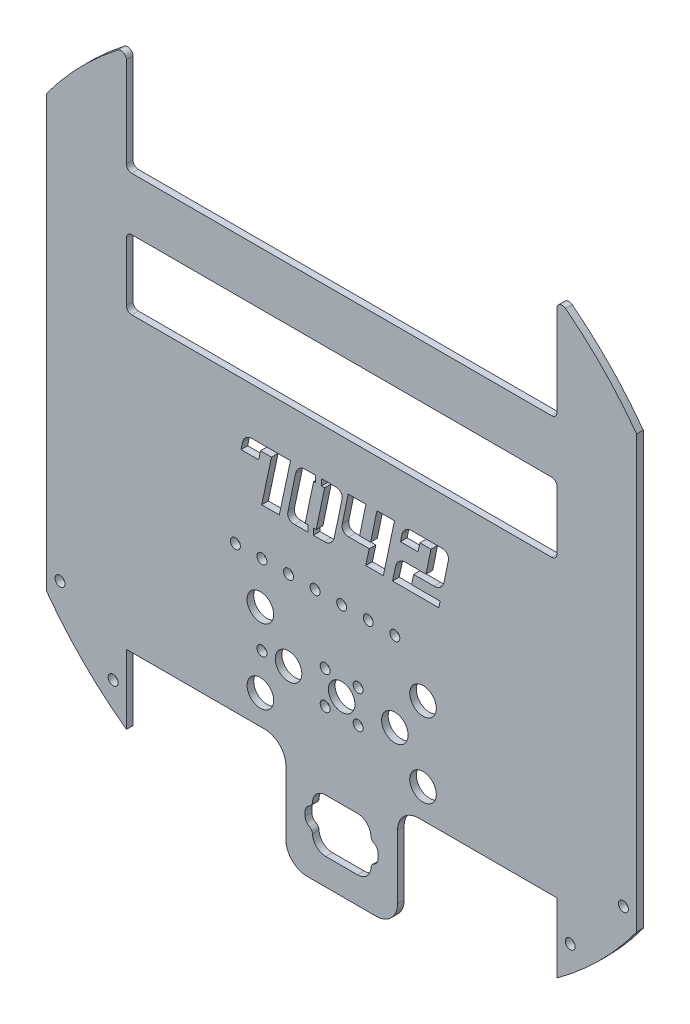
SolidWorks part; units mm, degrees
material "6061 Alloy"
ref_plane "Front Plane" through (0, 0, 0) normal (0, 0, 1) x (1, 0, 0)
ref_plane "Top Plane" through (0, 0, 0) normal (0, 1, 0) x (1, 0, 0)
ref_plane "Right Plane" through (0, 0, 0) normal (1, 0, 0) x (0, 0, -1)
sketch "Sketch1" plane through (0, 0, 0) normal (0, 0, 1) x (1, 0, 0)
  line L1 (-140.9655, 145.0225) -> (-102.8655, 145.0225)
  line L2 (-140.9655, 145.0225) -> (-140.9655, -145.0225)
  line L3 (-140.9655, -145.0225) -> (-102.8655, -145.0225)
  line L4 (-102.8655, 145.0225) -> (-102.8655, -145.0225)
  line L5 (-140.9655, 145.0225) -> (-102.8655, -145.0225) construction
  line L6 (-140.9655, -145.0225) -> (-102.8655, 145.0225) construction
  line L7 (-140.9655, 31.75) -> (140.9655, 31.75)
  line L8 (-140.9655, 31.75) -> (-140.9655, -31.75)
  line L9 (-140.9655, -31.75) -> (140.9655, -31.75)
  line L10 (140.9655, 31.75) -> (140.9655, -31.75)
  line L11 (-140.9655, 31.75) -> (140.9655, -31.75) construction
  line L12 (-140.9655, -31.75) -> (140.9655, 31.75) construction
  line L13 (102.8655, 145.0225) -> (140.9655, 145.0225)
  line L14 (102.8655, 145.0225) -> (102.8655, -145.0225)
  line L15 (102.8655, -145.0225) -> (140.9655, -145.0225)
  line L16 (140.9655, 145.0225) -> (140.9655, -145.0225)
  line L17 (102.8655, 145.0225) -> (140.9655, -145.0225) construction
  line L18 (102.8655, -145.0225) -> (140.9655, 145.0225) construction
  line L19 (-140.9655, -31.75) -> (140.9655, -31.75)
  line L20 (-140.9655, -31.75) -> (-140.9655, -69.85)
  line L21 (-140.9655, -69.85) -> (140.9655, -69.85)
  line L22 (140.9655, -31.75) -> (140.9655, -69.85)
  circle A0 centre (0, 0) radius 177.8
  circle A7 centre (0, -38.1) radius 25.4 construction
  circle A8 centre (-25.4, -38.1) radius 2.3813
  circle A9 centre (25.4, -38.1) radius 2.3813
  circle A10 centre (0, -38.1) radius 2.3812
  point P3 (-121.9155, 0)
  point P12 (121.9155, 0)
  dimension "D1" = 355.6
  dimension "D5" = 50.8
  dimension "D6" = 38.1
  dimension "D7" = 281.9311
  dimension "D10" = 4.7625
  dimension "D8" = 4.7625
  dimension "D9" = 4.7625
  dimension "D2" = 38.1
  dimension "D3" = 38.1
  dimension "D4" = 63.5
  dimension "D12" = 38.1
extrude "Boss-Extrude1" add sketch "Sketch1" along normal blind 3.175 contours L4 A0 L2 L7 | L2 L9 L4 L7 | L14 L7 L4 L9 A8 | L2 A0 L4 L9 | L16 A0 L14 L7 | L7 L14 L9 L10 | L14 A0 L16 L9 | L19 A10 L9 L4 L21 L14 A9 A8 | L2 L21 L4 L9 | L14 L21 L16 L9 region at (-120.723, 80.7079, 0) region at (0, 0, 0) region at (-121.9155, 0, 0) region at (120.723, 80.7079, 0) region at (-119.9486, -100.1295, 0) region at (0, -50.8872, 0) region at (-121.9155, -50.8, 0) region at (121.9155, 0, 0) region at (121.9155, -50.8, 0) region at (119.9486, -100.1295, 0)
sketch "Sketch2" plane through (0, 0, 3.175) normal (0, 0, 1) x (1, 0, 0)
  line L0 (-140.9655, -103.066) -> (-140.9655, -108.3585)
  line L1 (-140.9655, 108.3585) -> (-140.9655, -108.3585) construction
  line L2 (-102.8655, -141.1119) -> (-102.8655, -145.0225)
  line L3 (102.8655, -141.1119) -> (102.8655, -145.0225)
  line L4 (102.8655, -69.85) -> (102.8655, -145.0225) construction
  line L5 (140.9655, -103.066) -> (140.9655, -108.3585)
  line L6 (140.9655, 108.3585) -> (140.9655, -108.3585) construction
  line L7 (-102.8655, -69.85) -> (-102.8655, -145.0225) construction
  circle A0 centre (0, 0) radius 177.8
  circle A1 centre (0, 0) radius 174.625
  line M3 (-140.9655, 108.3585) -> (-140.9655, -108.3585)
  arc M4 (-140.9655, -108.3585) -> (-102.8655, -145.0225) centre (0, 0) ccw
  line M5 (-102.8655, -145.0225) -> (-102.8655, -69.85)
  line M7 (102.8655, -69.85) -> (102.8655, -145.0225)
  arc M8 (102.8655, -145.0225) -> (140.9655, -108.3585) centre (0, 0) ccw
  line M9 (140.9655, -108.3585) -> (140.9655, 108.3585)
  dimension "D1" = 355.6
  dimension "D2" = 349.25
extrude "Boss-Extrude2" add sketch "Sketch2" along normal blind 50.8 contours A1 M3 M4 M5 | A1 M7 M8 M9 region at (-122.8631, -125.3578, 3.175) region at (122.8631, -125.3578, 3.175)
sketch "Sketch3" plane through (0, 0, 3.175) normal (0, 0, 1) x (1, 0, 0)
  circle A0 centre (0, 0) radius 174.625
  circle A1 centre (0, 0) radius 203.8293
  dimension "D1" = 349.25
extrude "Cut-Extrude1" cut sketch "Sketch3" along normal through all and the other way through all
sketch "Sketch5" plane through (0, 0, 3.175) normal (0, 0, 1) x (1, 0, 0)
  line L0 (0, 165.1) -> (0, -165.1) construction
  line L1 (102.8655, -69.85) -> (102.8655, -141.1119) construction
  circle A0 centre (0, 0) radius 165.1 construction
  circle A1 centre (134.6155, -95.5859) radius 2.3813
  circle A2 centre (109.2155, -123.8143) radius 2.3813
  circle A3 centre (-134.6155, -95.5859) radius 2.3813
  circle A4 centre (-109.2155, -123.8143) radius 2.3813
  arc A5 (140.9655, 103.066) -> (102.8655, 141.1119) centre (0, 0) ccw construction
  dimension "D1" = 330.2
  dimension "D3" = 4.7625
  dimension "D4" = 4.7625
  dimension "D2" = 25.4
  dimension "D5" = 6.35
extrude "Cut-Extrude3" cut sketch "Sketch5" against normal through all
sketch "Sketch6" plane through (0, 0, 3.175) normal (0, 0, 1) x (1, 0, 0)
  line L0 (-102.8655, 141.1119) -> (-102.8655, 31.75) construction
  line L1 (-102.8655, 90.3119) -> (102.8655, 90.3119)
  line L2 (-102.8655, 90.3119) -> (-102.8655, 64.9119)
  line L3 (-102.8655, 64.9119) -> (102.8655, 64.9119)
  line L4 (102.8655, 90.3119) -> (102.8655, 64.9119)
  line L5 (102.8655, 141.1119) -> (102.8655, 31.75) construction
  dimension "D1" = 25.4
  dimension "D2" = 50.8
extrude "Boss-Extrude3" add sketch "Sketch6" against normal blind 3.175
sketch "Sketch7" plane through (0, 0, 3.175) normal (0, 0, 1) x (1, 0, 0)
  line L0 (102.8655, 90.3119) -> (-102.8655, 90.3119) construction
  line L1 (-157.8266, 90.3119) -> (153.0605, 90.3119)
  line L2 (-157.8266, 90.3119) -> (-157.8266, 162.3702)
  line L3 (-157.8266, 162.3702) -> (153.0605, 162.3702)
  line L4 (153.0605, 90.3119) -> (153.0605, 162.3702)
extrude "Cut-Extrude4" [suppressed] cut sketch "Sketch7" against normal through all
sketch "Sketch8" plane through (0, 0, 3.175) normal (0, 0, 1) x (1, 0, 0)
  circle A0 centre (0, -38.1) radius 38.1 construction
  circle A1 centre (-38.1, -38.1) radius 2.3812
  circle A2 centre (0, -38.1) radius 50.8 construction
  circle A3 centre (-50.8, -38.1) radius 2.3812
  circle A4 centre (0, -38.1) radius 12.7 construction
  circle A5 centre (12.7, -38.1) radius 2.3812
  circle A6 centre (-12.7, -38.1) radius 2.3812
  dimension "D1" = 76.2
  dimension "D2" = 4.7625
  dimension "D3" = 101.6
  dimension "D4" = 4.7625
  dimension "D5" = 25.4
  dimension "D6" = 4.7625
  dimension "D7" = 4.7625
extrude "Cut-Extrude5" cut sketch "Sketch8" against normal through all
sketch "Sketch9" plane through (0, 0, 3.175) normal (0, 0, 1) x (1, 0, 0)
  line L0 (102.8655, -69.85) -> (102.8655, -141.1119) construction
  line L1 (-102.8655, -69.85) -> (102.8655, -69.85)
  line L2 (-102.8655, -69.85) -> (-102.8655, -107.95)
  line L3 (-102.8655, -107.95) -> (102.8655, -107.95)
  line L4 (102.8655, -69.85) -> (102.8655, -107.95)
  dimension "D1" = 38.1
extrude "Boss-Extrude4" add sketch "Sketch9" against normal blind 3.175
sketch "Sketch10" plane through (0, 0, 3.175) normal (0, 0, 1) x (1, 0, 0)
  circle A0 centre (0, -76.2) radius 6.35
  circle A1 centre (0, -38.1) radius 2.3812 construction
  circle A2 centre (0, -76.2) radius 25.4 construction
  circle A3 centre (0, -76.2) radius 38.1 construction
  circle A4 centre (-25.4, -76.2) radius 2.3813
  circle A5 centre (-38.1, -76.2) radius 2.3812
  circle A6 centre (25.4, -76.2) radius 2.3813
  dimension "D1" = 38.1
  dimension "D2" = 12.7
  dimension "D3" = 50.8
  dimension "D4" = 76.2
  dimension "D5" = 4.7625
  dimension "D6" = 4.7625
  dimension "D7" = 4.7625
extrude "Cut-Extrude6" cut sketch "Sketch10" against normal through all
sketch "Sketch11" plane through (0, 0, 3.175) normal (0, 0, 1) x (1, 0, 0)
  line L0 (-102.8655, -107.95) -> (102.8655, -107.95) construction
  line L1 (-26.6655, -107.95) -> (26.6655, -107.95)
  line L2 (-26.6655, -107.95) -> (-26.6655, -158.75)
  line L3 (-26.6655, -158.75) -> (26.6655, -158.75)
  line L4 (26.6655, -107.95) -> (26.6655, -158.75)
  line L5 (-102.8655, -107.95) -> (-102.8655, -141.1119) construction
  line L6 (102.8655, -107.95) -> (102.8655, -141.1119) construction
  dimension "D1" = 50.8
  dimension "D2" = 76.2
  dimension "D3" = 76.2
extrude "Boss-Extrude5" add sketch "Sketch11" against normal blind 3.175
fillet "Fillet1" radius 10.16 4 edges at (26.6655, -107.95, 1.5875) (-26.6655, -107.95, 1.5875) (-26.6655, -158.75, 1.5875) (26.6655, -158.75, 1.5875)
sketch "Sketch12" plane through (0, 0, 3.175) normal (0, 0, 1) x (1, 0, 0)
  line L1 (-12.7, -63.5) -> (12.7, -63.5) construction
  line L2 (-12.7, -63.5) -> (-12.7, -88.9) construction
  line L3 (-12.7, -88.9) -> (12.7, -88.9) construction
  line L4 (12.7, -63.5) -> (12.7, -88.9) construction
  circle A0 centre (-25.4, -76.2) radius 6.35
  circle A1 centre (25.4, -76.2) radius 6.35
  circle A2 centre (0, -76.2) radius 6.35 construction
  circle A3 centre (-7.874, -68.326) radius 2.3812
  circle A7 centre (7.874, -68.326) radius 2.3813
  circle A8 centre (7.874, -84.074) radius 2.3812
  circle A9 centre (-7.874, -84.074) radius 2.3812
  point P23 (0, -76.2)
  point P24 (0, -76.2)
  dimension "D1" = 12.7
  dimension "D2" = 12.7
  dimension "D7" = 4.826
  dimension "D9" = 4.7625
  dimension "D3" = 12.7
  dimension "D4" = 25.4
  dimension "D5" = 12.7
  dimension "D6" = 25.4
  dimension "D8" = 4.826
  dimension "D10" = 4
extrude "Cut-Extrude7" cut sketch "Sketch12" against normal through all
fillet "Fillet2" radius 2.54 2 edges at (102.8655, 141.1119, 1.5875) (-102.8655, 141.1119, 1.5875)
sketch "Sketch13" plane through (0, 0, 3.175) normal (0, 0, 1) x (1, 0, 0)
  line L0 (-140.9655, -16.1069) -> (140.9655, -16.1069) construction
  line L1 (-140.9655, 103.066) -> (-140.9655, -103.066) construction
  line L2 (140.9655, 103.066) -> (140.9655, -103.066) construction
  text T0 "7042" font "Aero" height 25.4
extrude "Cut-Extrude8" cut sketch "Sketch13" against normal through all
sketch "Sketch14" plane through (0, 0, 3.175) normal (0, 0, 1) x (1, 0, 0)
  line L1 (-12.3972, 11.8715) -> (-9.6379, 11.8715)
  line L2 (-12.3972, 11.8715) -> (-12.3972, 3.9079)
  line L3 (-12.3972, 3.9079) -> (-9.6379, 3.9079)
  line L4 (-9.6379, 11.8715) -> (-9.6379, 3.9079)
  line L5 (-16.0587, -11.8105) -> (-13.5317, -11.8105)
  line L6 (-16.0587, -11.8105) -> (-16.0587, -17.7494)
  line L7 (-16.0587, -17.7494) -> (-13.5317, -17.7494)
  line L8 (-13.5317, -11.8105) -> (-13.5317, -17.7494)
extrude "Boss-Extrude6" add sketch "Sketch14" against normal blind 3.175
fillet "Fillet3" radius 2.54 6 edges at (-102.8655, 90.3119, 1.5875) (102.8655, 90.3119, 1.5875) (102.8655, 31.75, 1.5875) (102.8655, 64.9119, 1.5875) (-102.8655, 31.75, 1.5875) (-102.8655, 64.9119, 1.5875)
sketch "Sketch15" plane through (0, 0, 3.175) normal (0, 0, 1) x (1, 0, 0)
  line L0 (-26.6655, -118.11) -> (-26.6655, -148.59) construction
  line L1 (-7.6155, -120.65) -> (7.6155, -120.65)
  line L2 (-13.9655, -127) -> (-13.9655, -139.7)
  line L3 (-7.6155, -146.05) -> (7.6155, -146.05)
  line L4 (13.9655, -127) -> (13.9655, -139.7)
  line L5 (-13.9655, -120.65) -> (13.9655, -146.05) construction
  line L6 (-13.9655, -146.05) -> (13.9655, -120.65) construction
  line L7 (26.6655, -148.59) -> (26.6655, -118.11) construction
  line L8 (-16.5055, -158.75) -> (16.5055, -158.75) construction
  arc A0 (-13.9655, -139.7) -> (-7.6155, -146.05) centre (-7.6155, -139.7) ccw
  arc A1 (7.6155, -146.05) -> (13.9655, -139.7) centre (7.6155, -139.7) ccw
  arc A2 (7.6155, -120.65) -> (13.9655, -127) centre (7.6155, -127) cw
  arc A3 (-7.6155, -120.65) -> (-13.9655, -127) centre (-7.6155, -127) ccw
  point P0 (0, -133.35)
  dimension "D5" = 6.35
  dimension "D1" = 12.7
  dimension "D2" = 12.7
  dimension "D3" = 12.7
  dimension "D4" = 25.4
extrude "Cut-Extrude9" cut sketch "Sketch15" against normal through all
sketch "Sketch16" plane through (0, 0, 3.175) normal (0, 0, 1) x (1, 0, 0)
  line L0 (-13.9655, -133.35) -> (13.9655, -133.35) construction
  line L1 (-13.6525, -128.5875) -> (13.6525, -128.5875)
  line L2 (-17.4625, -132.3975) -> (-17.4625, -134.3025)
  line L3 (-13.6525, -138.1125) -> (13.6525, -138.1125)
  line L4 (17.4625, -132.3975) -> (17.4625, -134.3025)
  line L5 (-17.4625, -128.5875) -> (17.4625, -138.1125) construction
  line L6 (-17.4625, -138.1125) -> (17.4625, -128.5875) construction
  line L7 (-13.9655, -127) -> (-13.9655, -139.7) construction
  line L8 (13.9655, -139.7) -> (13.9655, -127) construction
  arc A0 (13.6525, -138.1125) -> (17.4625, -134.3025) centre (13.6525, -134.3025) ccw
  arc A1 (13.6525, -128.5875) -> (17.4625, -132.3975) centre (13.6525, -132.3975) cw
  arc A2 (-17.4625, -134.3025) -> (-13.6525, -138.1125) centre (-13.6525, -134.3025) ccw
  arc A3 (-13.6525, -128.5875) -> (-17.4625, -132.3975) centre (-13.6525, -132.3975) ccw
  point P0 (0, -133.35)
  point P11 (0, 0)
  dimension "D3" = 3.81
  dimension "D1" = 9.525
  dimension "D2" = 34.925
extrude "Cut-Extrude10" cut sketch "Sketch16" against normal through all
fillet "Fillet4" radius 2.54 4 edges at (13.9655, -138.0996, 1.5875) (13.9655, -128.6004, 1.5875) (-13.9655, -138.0996, 1.5875) (-13.9655, -128.6004, 1.5875)
sketch "Sketch17" plane through (0, 0, 3.175) normal (0, 0, 1) x (1, 0, 0)
  line L0 (0, -69.85) -> (0, -82.55) construction
  line L1 (-6.35, -76.2) -> (6.35, -76.2) construction
  circle A0 centre (38.862, -93.98) radius 6.35
  circle A1 centre (0, -76.2) radius 6.35 construction
  circle A2 centre (0, -76.2) radius 6.35 construction
  circle A3 centre (-38.862, -93.98) radius 6.35
  circle A4 centre (38.862, -58.42) radius 6.35
  circle A5 centre (-38.862, -58.42) radius 6.35
  dimension "D1" = 38.862
  dimension "D2" = 17.78
  dimension "D3" = 12.7
extrude "Cut-Extrude11" cut sketch "Sketch17" against normal through all
